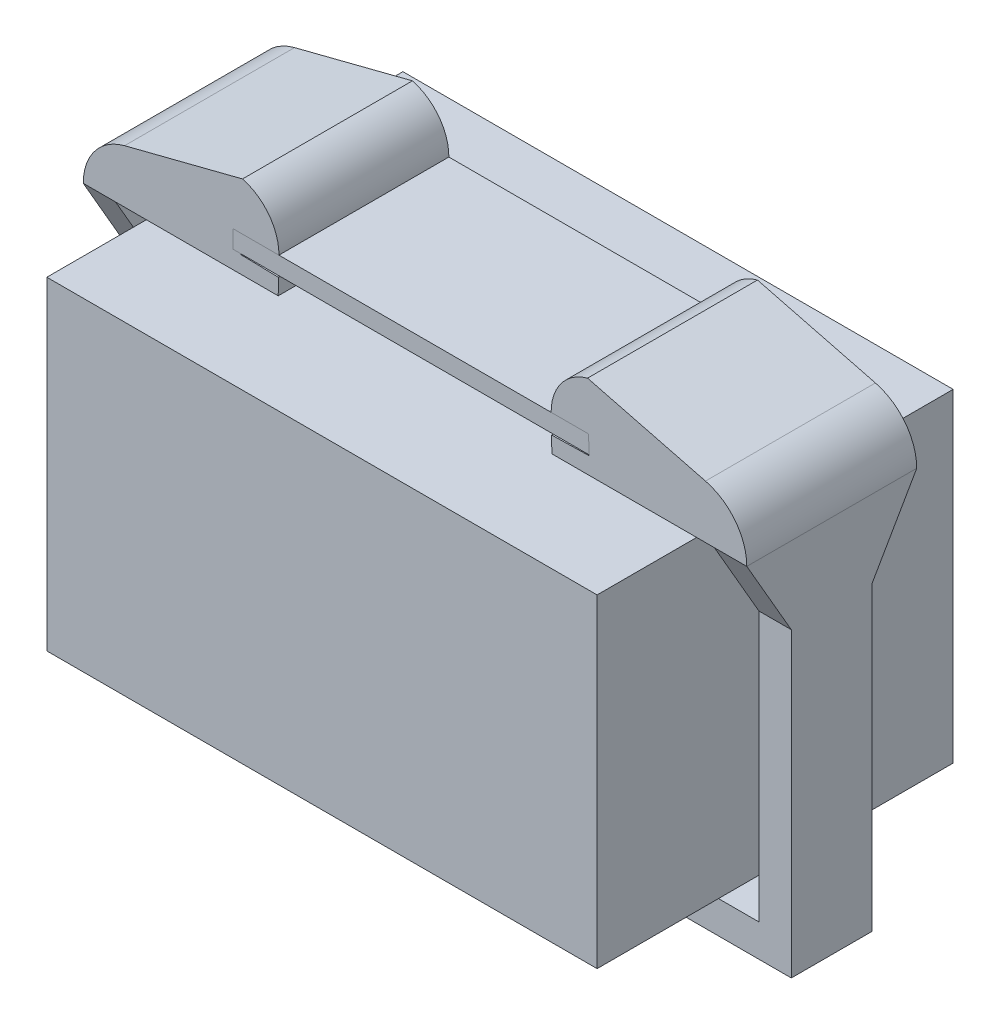
SolidWorks part; units mm, degrees
ref_plane "Front Plane" through (0, 0, 0) normal (0, 0, 1) x (1, 0, 0)
ref_plane "Top Plane" through (0, 0, 0) normal (0, 1, 0) x (1, 0, 0)
ref_plane "Right Plane" through (0, 0, 0) normal (1, 0, 0) x (0, 0, -1)
sketch "Sketch1" plane through (0, 0, 0) normal (0, 1, 0) x (1, 0, 0)
  line L9 (-22.5, -10.5) -> (22.5, -10.5)
  line L10 (-22.5, -10.5) -> (-22.5, 10.5)
  line L11 (-22.5, 10.5) -> (22.5, 10.5)
  line L12 (22.5, -10.5) -> (22.5, 10.5)
  line L13 (-22.5, -10.5) -> (22.5, 10.5) construction
  line L14 (-22.5, 10.5) -> (22.5, -10.5) construction
  point P0 (0, 0)
  point P1 (0, 0)
  point P7 (0, 0)
  dimension "D2" = 21
  dimension "D3" = 45
extrude "Boss-Extrude1" add sketch "Sketch1" along normal blind 2.2
ref_plane "Plane1" through (0, -3, 0) normal (0, -1, 0) x (-1, 0, 0)
sketch "Sketch2" plane through (0, -3, 0) normal (0, 1, 0) x (1, 0, 0)
  line L1 (-34, -22) -> (34, -22)
  line L2 (-34, -22) -> (-34, 22)
  line L3 (-34, 22) -> (34, 22)
  line L4 (34, -22) -> (34, 22)
  line L5 (-34, -22) -> (34, 22) construction
  line L6 (-34, 22) -> (34, -22) construction
  point P0 (0, 0)
  dimension "D1" = 44
  dimension "D2" = 68
extrude "Boss-Extrude2" add sketch "Sketch2" against normal blind 40 separate body
sketch "Sketch3" plane through (0, 0, 0) normal (0, 0, 1) x (1, 0, 0)
  line L0 (-34, -43) -> (34, -43) construction
  line L1 (-21.5, -57.7) -> (21.5, -57.7) construction
  line L2 (-21.5, -57.7) -> (-21.5, -45) construction
  line L3 (-21.5, -45) -> (21.5, -45) construction
  line L4 (21.5, -57.7) -> (21.5, -45) construction
  line L5 (-21.5, -57.7) -> (21.5, -45) construction
  line L6 (-21.5, -45) -> (21.5, -57.7) construction
  line L7 (22.5, 2.2) -> (22.5, 0) construction
  line L8 (0, -24.2) -> (0, 24.2) construction
  line L10 (21.5, -57.7) -> (25.5, -57.7) construction
  line L11 (21.5, -57.7) -> (21.5, 0) construction
  line L13 (25.5, -57.7) -> (25.5, 0) construction
  line L16 (-25.5, -57.7) -> (-25.5, 0) construction
  line L17 (-21.5, -57.7) -> (-25.5, -57.7) construction
  line L18 (-21.5, -57.7) -> (-21.5, 0) construction
  line L20 (21.5, -45) -> (22.5, 0) construction
  line L21 (24.2, 0) -> (-24.2, 0) construction
  line L22 (25.5, 0) -> (25.3178, 8.198) construction
  line L23 (25.5, 0) -> (25.5, 5.5196)
  line L24 (25.3178, 8.198) -> (21.3188, 8.1091) construction
  line L26 (21.5, 0) -> (21.4511, 2.1995) construction
  line L27 (16.8188, 2.0965) -> (21.4511, 2.1995) construction
  line L28 (-21.5, 0) -> (-21.4511, 2.1995) construction
  line L29 (-16.8188, 2.0965) -> (-21.4511, 2.1995) construction
  line L30 (-25.5, 0) -> (-25.3178, 8.198) construction
  line L31 (-25.3178, 8.198) -> (-21.3188, 8.1091) construction
  circle A2 centre (0, -51.35) radius 2.5 construction
  arc A3 (21.3188, 8.1091) -> (16.8188, 2.0965) centre (22.9049, 2.2318) ccw construction
  arc A4 (-21.3188, 8.1091) -> (-16.8188, 2.0965) centre (-22.9049, 2.2318) cw construction
  point P0 (0, -51.35)
  dimension "D8" = 5
  dimension "D1" = 2
  dimension "D2" = 12.7
  dimension "D3" = 1
  dimension "D7" = 4
  dimension "D9" = 1.273
  dimension "D4" = 8.2
  dimension "D5" = 1.273
  dimension "D6" = 4.5
  dimension "D10" = 2.2
sketch "Sketch4" plane through (0, 0, 0) normal (0, 0, 1) x (1, 0, 0)
  line L1 (-37, -45) -> (37, -45)
  line L2 (-37, -45) -> (-37, -49)
  line L3 (-37, -49) -> (-25.5, -49)
  line L4 (37, -45) -> (37, -49)
  line L5 (34, -43) -> (34, -3) construction
  line L6 (-34, -43) -> (34, -43) construction
  line L7 (21.3188, 8.1091) -> (35.8931, 4.3797)
  line L8 (37, -49) -> (41, -49)
  line L9 (37, -49) -> (37, -2.1985)
  line L11 (41, -49) -> (41, -2.1985)
  line L12 (22.5, 0) -> (22.5, -45) construction
  line L13 (16.8188, 2.0965) -> (21.4511, 2.1995) construction
  line L14 (-25.5, -57.7) -> (-25.5, 0) construction
  line L16 (16.8188, 2.0965) -> (21.4511, 2.1995)
  line L17 (0, -24.2) -> (0, 24.2) construction
  line L19 (21.4511, 2.1995) -> (21.5, -0.1005)
  line L20 (21.5, -57.7) -> (21.5, 0) construction
  line L21 (21.5, -0.1005) -> (16.8676, -0.199)
  line L22 (16.8676, -0.199) -> (16.9101, -2.1985)
  line L23 (16.9101, -2.1985) -> (37, -2.1985)
  line L24 (2.1213, -49) -> (37, -49)
  line L25 (37, -49) -> (25.5, -49)
  line L26 (37, -2.1985) -> (41, -2.1985)
  line L27 (-37, -49) -> (-41, -49)
  line L28 (-41, -49) -> (-41, -2.1985)
  line L29 (-37, -49) -> (-37, -2.1985)
  line L30 (-37, -2.1985) -> (-41, -2.1985)
  line L31 (-16.9101, -2.1985) -> (-37, -2.1985)
  line L32 (-16.8676, -0.199) -> (-16.9101, -2.1985)
  line L33 (-21.5, -0.1005) -> (-16.8676, -0.199)
  line L34 (-21.4511, 2.1995) -> (-21.5, -0.1005)
  line L35 (-16.8188, 2.0965) -> (-21.4511, 2.1995)
  line L36 (-21.3188, 8.1091) -> (-35.8931, 4.3797)
  line L37 (-41, -2.1985) -> (-37, -2.1985) construction
  arc A2 (21.3188, 8.1091) -> (16.8188, 2.0965) centre (22.9049, 2.2318) ccw construction
  arc A3 (35.8931, 4.3797) -> (41, -2.1985) centre (34.2098, -2.1985) cw
  arc A4 (21.3188, 8.1091) -> (16.8188, 2.0965) centre (22.9049, 2.2318) ccw
  arc A5 (-25.5, -49) -> (25.5, -49) centre (0, 7.3636) ccw
  circle A6 centre (0, -49.75) radius 2.25
  arc A7 (-21.3188, 8.1091) -> (-16.8188, 2.0965) centre (-22.9049, 2.2318) cw
  arc A8 (-35.8931, 4.3797) -> (-41, -2.1985) centre (-34.2098, -2.1985) ccw
  point P38 (0, -54.5)
  dimension "D9" = 4.5
  dimension "D10" = 2.5
  dimension "D11" = 2.5
  dimension "D1" = 2
  dimension "D2" = 3
  dimension "D4" = 4
  dimension "D5" = 2.7902
  dimension "D6" = 4
  dimension "D7" = 2.3
  dimension "D8" = 2
extrude "Boss-Extrude3" add sketch "Sketch4" along normal blind 5 and the other way blind 5 separate body contours L29 L30 L28 L27 L2 | A6 L24 L4 L1 L2 L3 A5 | L26 L9 L4 L8 L11 region at (0, -45.7461, 0) region at (-39, -25.5993, 0) region at (39, -25.5993, 0)
extrude "Boss-Extrude4" add sketch "Sketch4<4>" along normal up to vertex (-10.5 mm away) and the other way up to vertex (10.5 mm away) contours L7 A4 L16 L19 L21 L22 L23 L26 A3 | L36 A8 L30 L31 L32 L33 L34 L35 A7 region at (-28.0509, 1.9759, 0) region at (28.0509, 1.9759, 0) up to point (22.5, 0, -10.5) other way up to point (22.5, 0, -10.5)
sketch "Sketch4<4>" plane through (0, 0, 0) normal (0, 0, 1) x (1, 0, 0) same geometry as "Sketch4"
sketch "Sketch6" plane through (41, 0, 0) normal (1, 0, 0) x (0, 0, -1)
  line L0 (10.5, -2.1985) -> (5, -11.7248)
  line L1 (5, -49) -> (5, -2.1985) construction
  line L2 (5, -11.7248) -> (5, -2.1985)
  line L3 (5, -2.1985) -> (10.5, -2.1985)
  line L4 (0, 36.2439) -> (0, -36.2439) construction
  line L5 (-5, -11.7248) -> (-5, -2.1985)
  line L6 (-10.5, -2.1985) -> (-5, -11.7248)
  line L7 (-5, -2.1985) -> (-10.5, -2.1985)
  dimension "D1" = 30
extrude "Boss-Extrude5" add sketch "Sketch6" against normal up to vertex (4 mm away) up to point (37, -2.1985, -5)
mirror "Mirror1" about plane through (0, 0, 0) normal (1, 0, 0) of "Boss-Extrude5"
equation "\"D5@Sketch3\"=\"D9@Sketch3\""
